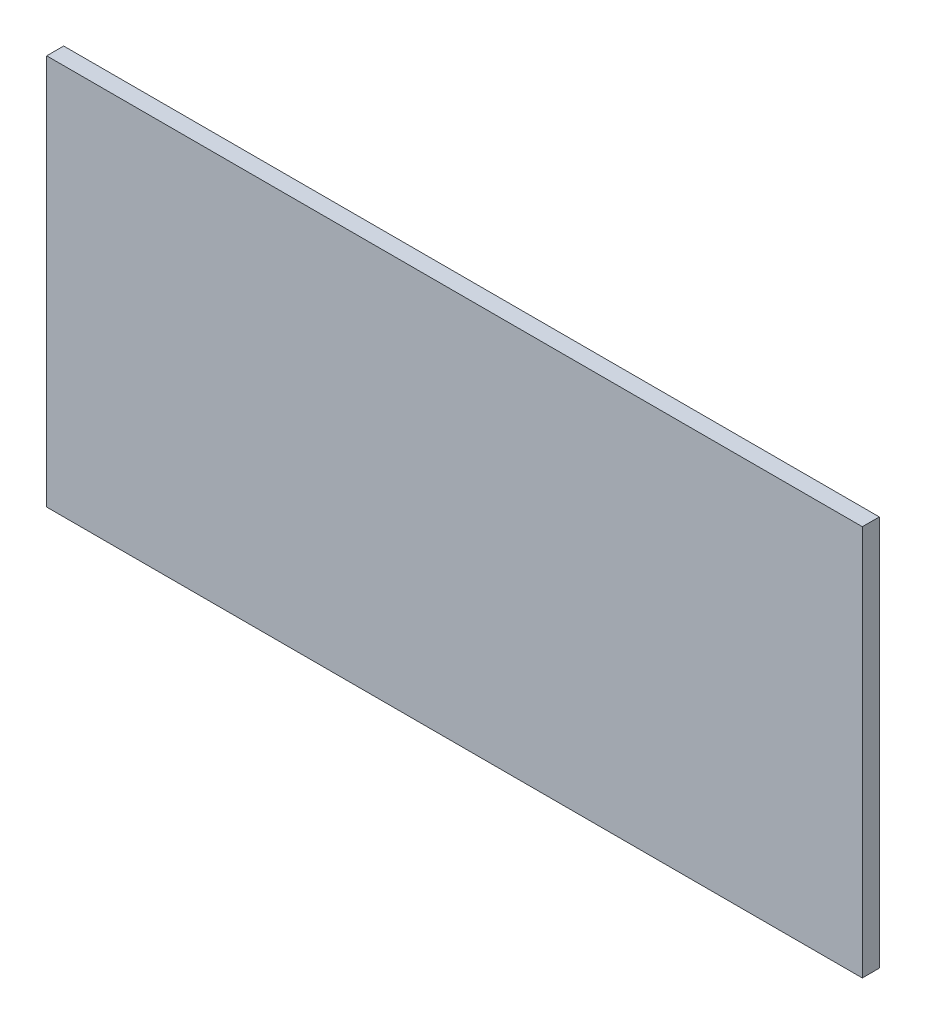
SolidWorks part; units mm, degrees
material "6061-T4 (SS)"
ref_plane "Front Plane" through (0, 0, 0) normal (0, 0, 1) x (1, 0, 0)
ref_plane "Top Plane" through (0, 0, 0) normal (0, 1, 0) x (1, 0, 0)
ref_plane "Right Plane" through (0, 0, 0) normal (1, 0, 0) x (0, 0, -1)
sketch "Sketch1" plane through (0, 0, 0) normal (0, 0, 1) x (1, 0, 0)
  line L1 (0, 0) -> (96, 0)
  line L2 (0, 0) -> (0, 46)
  line L3 (0, 46) -> (96, 46)
  line L4 (96, 0) -> (96, 46)
  dimension "D1" = 46
  dimension "D2" = 96
extrude "Boss-Extrude1" add sketch "Sketch1" along normal blind 2
